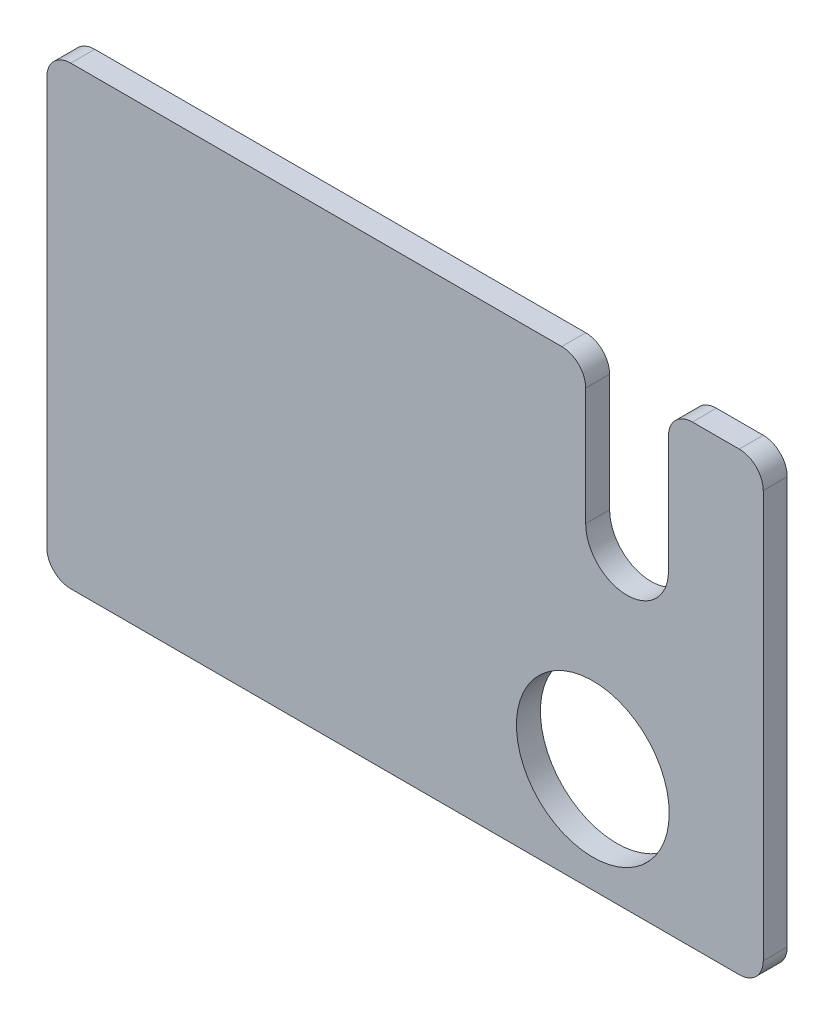
SolidWorks part; units mm, degrees
ref_plane "Front Plane" through (0, 0, 0) normal (0, 0, 1) x (1, 0, 0)
ref_plane "Top Plane" through (0, 0, 0) normal (0, 1, 0) x (1, 0, 0)
ref_plane "Right Plane" through (0, 0, 0) normal (1, 0, 0) x (0, 0, -1)
sketch "Sketch1" plane through (0, 0, 0) normal (0, 0, 1) x (1, 0, 0)
  line L0 (-107.95, -28.9639) -> (-107.95, 28.9639) construction
  line L1 (-114.3, 72.5406) -> (28.4099, 72.5406)
  line L2 (-114.3, 72.5406) -> (-114.3, -48.0139)
  line L3 (-114.3, -48.0139) -> (75.438, -48.0139)
  line L4 (75.438, 72.5406) -> (75.438, -48.0139)
  line L5 (-6.35, -41.6639) -> (-101.6, -41.6639) construction
  line L6 (50.3301, 35.1155) -> (50.3301, 72.5406)
  line L7 (28.4099, 35.1155) -> (28.4099, 72.5406)
  line L8 (50.3301, 72.5406) -> (75.438, 72.5406)
  circle A0 centre (39.37, 35.1155) radius 10.9601 construction
  arc A1 (28.4099, 35.1155) -> (50.3301, 35.1155) centre (39.37, 35.1155) ccw
  circle A2 centre (30.3047, -20.2311) radius 20.2311 construction
  circle A3 centre (30.3047, -20.2311) radius 20.2311
  circle A4 centre (60.198, 47.1406) radius 6.4326 construction
  circle A5 centre (18.542, 47.1406) radius 6.4326 construction
  dimension "D3" = 15.24
  dimension "D4" = 25.4
  dimension "D1" = 6.35
  dimension "D2" = 6.35
extrude "Boss-Extrude1" add sketch "Sketch1" along normal blind 6.35
fillet "Fillet1" radius 6.35 6 edges at (-114.3, -48.0139, 3.175) (-114.3, 72.5406, 3.175) (75.438, -48.0139, 3.175) (28.4099, 72.5406, 3.175) (50.3301, 72.5406, 3.175) (75.438, 72.5406, 3.175)
